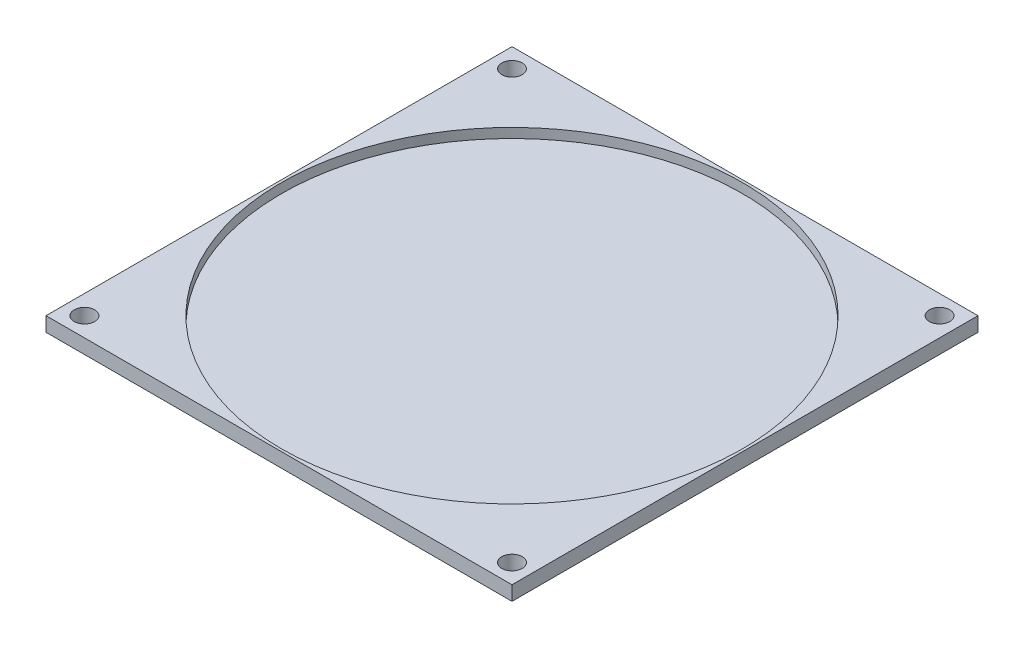
SolidWorks part; units mm, degrees
ref_plane "Front Plane" through (0, 0, 0) normal (0, 0, 1) x (1, 0, 0)
ref_plane "Top Plane" through (0, 0, 0) normal (0, 1, 0) x (1, 0, 0)
ref_plane "Right Plane" through (0, 0, 0) normal (1, 0, 0) x (0, 0, -1)
sketch "Sketch2" plane through (0, 0, 0) normal (0, 1, 0) x (1, 0, 0)
  line L1 (0, 0) -> (154.0002, 0)
  line L2 (0, 0) -> (0, 154.0002)
  line L3 (0, 154.0002) -> (154.0002, 154.0002)
  line L4 (154.0002, 0) -> (154.0002, 154.0002)
  dimension "D1" = 154.0002
  dimension "D2" = 154.0002
extrude "Boss-Extrude1" add sketch "Sketch2" along normal blind 4.7625
sketch "Sketch4" plane through (0, 4.7625, 0) normal (0, 1, 0) x (1, 0, 0)
  line L0 (0, 154.0002) -> (154.0002, 0) construction
  line L1 (0, 0) -> (154.0002, 154.0002) construction
  circle A0 centre (77.0001, 77.0001) radius 76.2
  dimension "D1" = 152.4
extrude "Cut-Extrude1" cut sketch "Sketch4" against normal blind 3.175
sketch "Sketch5" plane through (0, 4.7625, 0) normal (0, 1, 0) x (1, 0, 0)
  line L0 (6.35, 154.0002) -> (6.35, 147.6502) construction
  line L1 (154.0002, 154.0002) -> (0, 154.0002) construction
  line L3 (147.6502, 147.6502) -> (154.0002, 147.6502) construction
  line L4 (0, 154.0002) -> (0, 0) construction
  line L5 (154.0002, 0) -> (154.0002, 154.0002) construction
  line L6 (147.6502, 154.0002) -> (147.6502, 147.6502) construction
  line L7 (0, 147.6502) -> (6.35, 147.6502) construction
  line L8 (0, 6.35) -> (6.35, 6.35) construction
  line L9 (6.35, 6.35) -> (6.35, 0) construction
  line L10 (0, 0) -> (154.0002, 0) construction
  line L11 (147.6502, 0) -> (147.6502, 6.35) construction
  line L12 (147.6502, 6.35) -> (154.0002, 6.35) construction
  circle A0 centre (6.35, 6.35) radius 3.3782
  circle A1 centre (6.35, 147.6502) radius 3.3782
  circle A2 centre (147.6502, 147.6502) radius 3.3782
  circle A3 centre (147.6502, 6.35) radius 3.3782
  dimension "D8" = 6.7564
  dimension "D9" = 6.7564
  dimension "D10" = 6.7564
  dimension "D11" = 6.7564
  dimension "D1" = 6.35
  dimension "D2" = 6.35
  dimension "D3" = 6.35
  dimension "D4" = 6.35
  dimension "D5" = 6.35
  dimension "D6" = 6.35
  dimension "D7" = 6.35
extrude "Cut-Extrude2" cut sketch "Sketch5" against normal through all
